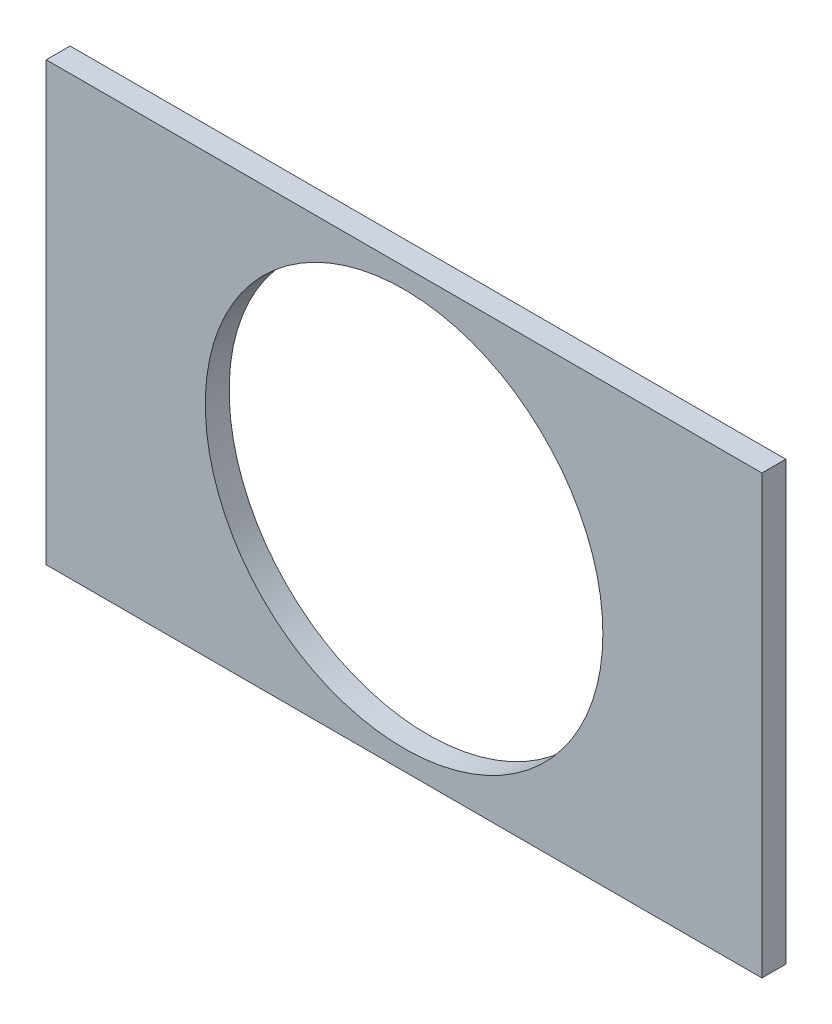
SolidWorks part; units mm, degrees
ref_plane "Front Plane" through (0, 0, 0) normal (0, 0, 1) x (1, 0, 0)
ref_plane "Top Plane" through (0, 0, 0) normal (0, 1, 0) x (1, 0, 0)
ref_plane "Right Plane" through (0, 0, 0) normal (1, 0, 0) x (0, 0, -1)
sketch "Sketch1" plane through (0, 0, 0) normal (0, 0, 1) x (1, 0, 0)
  line L1 (0, 0) -> (180, 0)
  line L2 (0, 0) -> (0, 110)
  line L3 (0, 110) -> (180, 110)
  line L4 (180, 0) -> (180, 110)
sketch "Sketch2" plane through (0, 0, 0) normal (0, 0, 1) x (1, 0, 0)
  circle A0 centre (90, 55) radius 50
extrude "Boss-Extrude1" add sketch "Sketch1" along normal blind 6 contours L3 L4 L1 L2
extrude "Cut-Extrude1" cut sketch "Sketch2" along normal blind 6
ref_plane "Plane1" through (0, 0, 6) normal (0, 0, 1) x (1, 0, 0)
sketch "Sketch3" plane through (0, 0, 6) normal (0, 0, 1) x (1, 0, 0)
  point P0 (90, 55)
